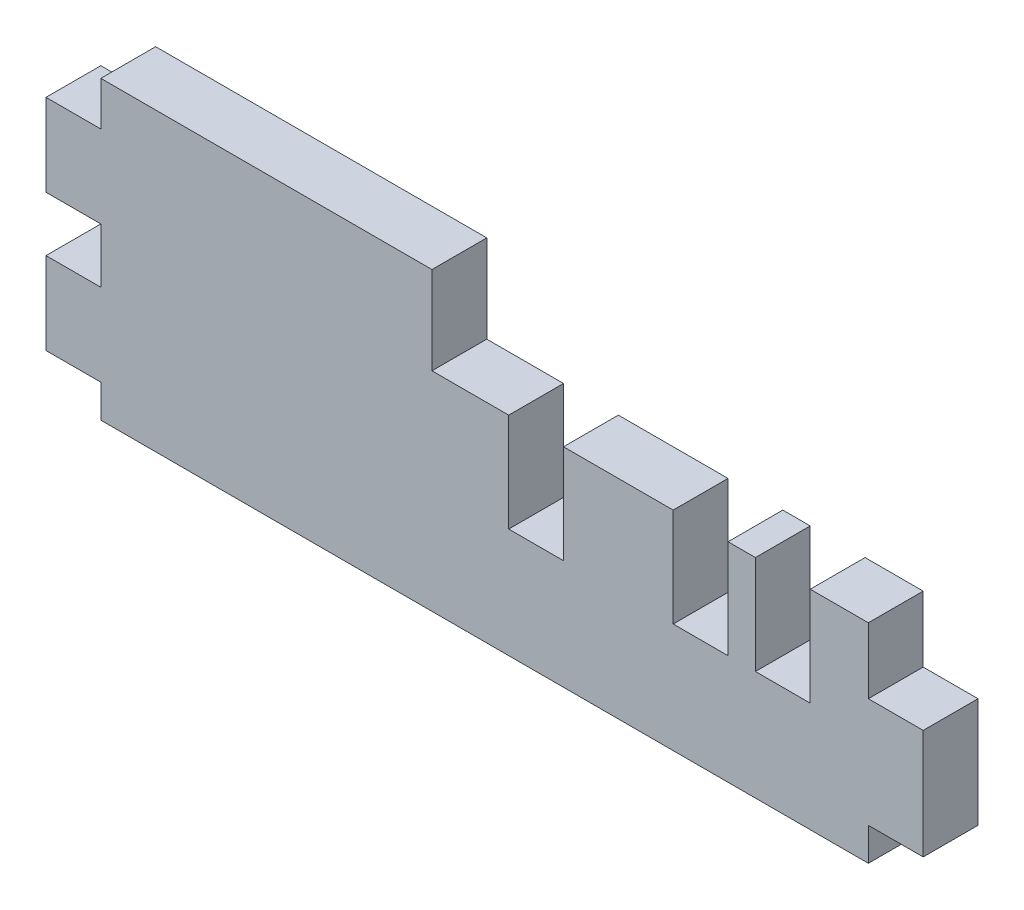
SolidWorks part; units mm, degrees
ref_plane "Plan de face" through (0, 0, 0) normal (0, 0, 1) x (1, 0, 0)
ref_plane "Plan de dessus" through (0, 0, 0) normal (0, 1, 0) x (1, 0, 0)
ref_plane "Plan de droite" through (0, 0, 0) normal (1, 0, 0) x (0, 0, -1)
sketch "Esquisse1" plane through (0, 0, 0) normal (0, 0, 1) x (1, 0, 0)
  line L0 (15.1, 0) -> (15.1, 24) construction
  line L1 (0, 0) -> (-5, 0)
  line L2 (0, 7.5) -> (0, 12.5)
  line L3 (0, 24) -> (30.2, 24)
  line L4 (30.2, 16) -> (30.2, 24)
  line L5 (0, 0) -> (0, -3)
  line L6 (-5, 20) -> (0, 20)
  line L7 (70, 0) -> (70, 10) construction
  line L8 (0, 12.5) -> (-5, 12.5)
  line L9 (-5, 20) -> (-5, 12.5)
  line L10 (0, 0) -> (-5, 0)
  line L11 (52.2, 7) -> (57.2, 7)
  line L12 (0, 7.5) -> (-5, 7.5)
  line L13 (-5, 0) -> (-5, 7.5)
  line L14 (30.2, 16) -> (37.2, 16)
  line L15 (70, 10) -> (70, 16)
  line L16 (70, 0) -> (75, 0)
  line L17 (52.2, 7) -> (52.2, 16)
  line L18 (70, 10) -> (75, 10)
  line L19 (75, 0) -> (75, 10)
  line L20 (64.7, 16) -> (70, 16)
  line L21 (57.2, 7) -> (57.2, 16)
  line L22 (57.2, 16) -> (59.7, 16)
  line L23 (0, 20) -> (0, 24)
  line L24 (59.7, 16) -> (59.7, 7)
  line L25 (59.7, 7) -> (64.7, 7)
  line L26 (64.7, 16) -> (64.7, 7)
  line L27 (42.2, 16) -> (52.2, 16)
  line L28 (70, 0) -> (70, -3)
  line L29 (70, -3) -> (0, -3)
  line L30 (37.2, 7) -> (42.2, 7)
  line L31 (37.2, 7) -> (37.2, 16)
  line L33 (42.2, 7) -> (42.2, 16)
  dimension "D1" = 16
  dimension "D2" = 24
  dimension "D3" = 75
  dimension "D4" = 7.5
  dimension "D5" = 5
  dimension "D6" = 5.3
  dimension "D7" = 2.5
  dimension "D8" = 3
  dimension "D9" = 30.2
  dimension "D10" = 5
  dimension "D11" = 10
  dimension "D12" = 9
  dimension "D13" = 10
  dimension "D14" = 3
  dimension "D15" = 5
extrude "Boss.-Extru.1" add sketch "Esquisse1" along normal blind 5 contours L29 L28 L16 L19 L18 L15 L20 L26 L25 L24 L22 L21 L11 L17 L14 L4 L3 L9 L8 L2 L12 L13 region at (29.8339, 8.2764, 0)
